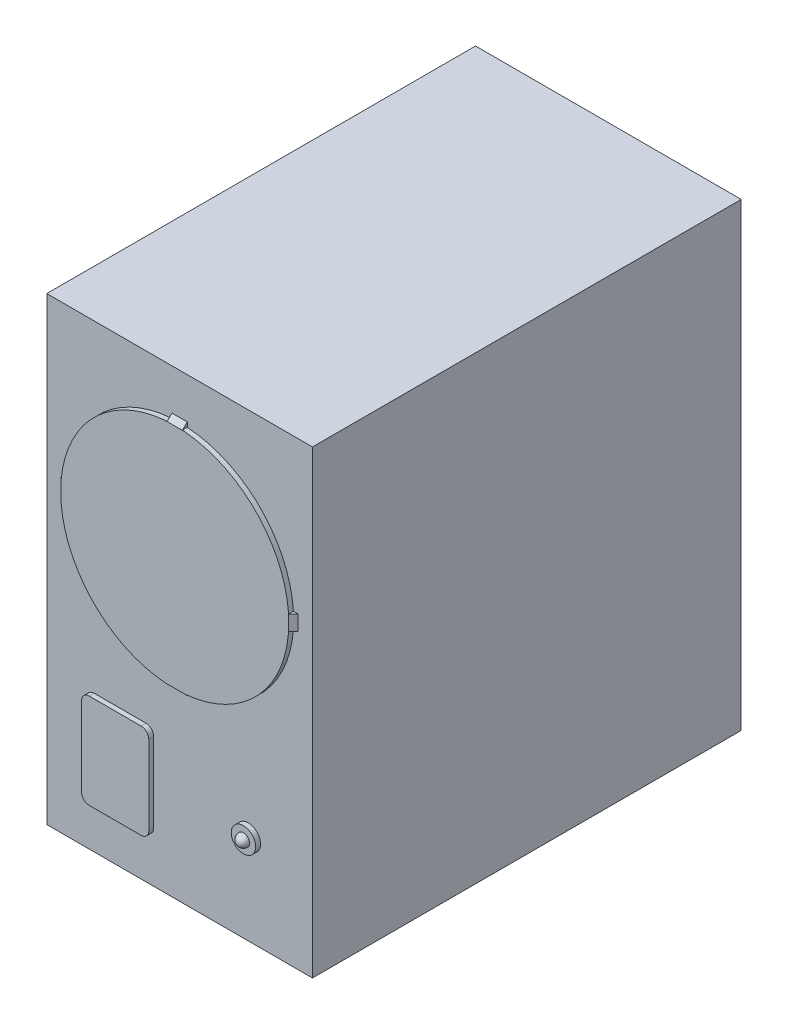
SolidWorks part; units mm, degrees
ref_plane "Plan de face" through (0, 0, 0) normal (0, 0, 1) x (1, 0, 0)
ref_plane "Plan de dessus" through (0, 0, 0) normal (0, 1, 0) x (1, 0, 0)
ref_plane "Plan de droite" through (0, 0, 0) normal (1, 0, 0) x (0, 0, -1)
sketch "Esquisse1" plane through (0, 0, 0) normal (0, 1, 0) x (1, 0, 0)
  line L0 (-43.5, 70.2) -> (43.5, -70.2) construction
  line L1 (-43.5, 70.2) -> (43.5, 70.2)
  line L2 (-43.5, 70.2) -> (-43.5, -70.2)
  line L3 (-43.5, -70.2) -> (43.5, -70.2)
  line L4 (43.5, 70.2) -> (43.5, -70.2)
  point P4 (0, 0)
  dimension "D1" = 87
  dimension "D2" = 140.4
extrude "Boss.-Extru.1" add sketch "Esquisse1" along normal blind 150.6
sketch "Esquisse2" plane through (0, 0, 70.2) normal (0, 0, 1) x (1, 0, 0)
  line L0 (-43.5, 150.6) -> (43.5, 150.6) construction
  line L1 (-43.5, 150.6) -> (43.5, 150.6)
  line L2 (0, 135.75) -> (0, 61.05) construction
  line L3 (-39.7, 100.9) -> (-37.2662, 100.9)
  line L4 (-39.7, 100.9) -> (-39.7, 95.9)
  line L5 (-39.7, 95.9) -> (-37.2662, 95.9)
  line L6 (-37.2662, 100.9) -> (-37.2662, 95.9)
  line L7 (-2.5, 138.1) -> (2.5, 138.1)
  line L8 (-2.5, 138.1) -> (-2.5, 135.6662)
  line L9 (-2.5, 135.6662) -> (2.5, 135.6662)
  line L10 (2.5, 138.1) -> (2.5, 135.6662)
  line L11 (-37.2662, 98.4) -> (37.35, 98.4) construction
  line L12 (37.2662, 100.9) -> (37.2662, 95.9)
  line L13 (39.7, 95.9) -> (37.2662, 95.9)
  line L14 (39.7, 100.9) -> (39.7, 95.9)
  line L15 (39.7, 100.9) -> (37.2662, 100.9)
  line L16 (2.5, 58.7) -> (2.5, 61.1338)
  line L17 (-2.5, 61.1338) -> (2.5, 61.1338)
  line L18 (-2.5, 58.7) -> (-2.5, 61.1338)
  line L19 (-2.5, 58.7) -> (2.5, 58.7)
  line L20 (-43.5, 150.6) -> (-43.5, 0) construction
  line L21 (-30.5, 45) -> (-8.5, 45)
  line L22 (-30.5, 45) -> (-30.5, 14)
  line L23 (-30.5, 14) -> (-8.5, 14)
  line L24 (-8.5, 45) -> (-8.5, 14)
  line L25 (-43.5, 0) -> (43.5, 0) construction
  line L26 (-30.5, 29.5) -> (-8.5, 29.5) construction
  line L27 (-19.5, 45) -> (-19.5, 14) construction
  line L28 (43.5, 150.6) -> (43.5, 0) construction
  arc A0 (-2.5, 135.6662) -> (-37.2662, 100.9) centre (0, 98.4) ccw
  arc A1 (-28, 45) -> (-30.5, 42.5) centre (-28, 42.5) ccw
  arc A2 (-11, 45) -> (-8.5, 42.5) centre (-11, 42.5) cw
  arc A3 (-11, 14) -> (-8.5, 16.5) centre (-11, 16.5) ccw
  arc A4 (-28, 14) -> (-30.5, 16.5) centre (-28, 16.5) cw
  circle A5 centre (22.5, 29.5) radius 4
  arc A6 (37.2662, 100.9) -> (2.5, 135.6662) centre (0, 98.4) ccw
  arc A7 (2.5, 61.1338) -> (37.2662, 95.9) centre (0, 98.4) ccw
  arc A8 (-37.2662, 95.9) -> (-2.5, 61.1338) centre (0, 98.4) ccw
  point P4 (0, 150.6)
  point P5 (0, 135.75)
  point P26 (0, 61.05)
  point P53 (26.5, 29.5)
  dimension "D1" = 74.7
  dimension "D9" = 5
  dimension "D10" = 8
  dimension "D2" = 5
  dimension "D3" = 12.5
  dimension "D4" = 79.4
  dimension "D5" = 31
  dimension "D6" = 22
  dimension "D7" = 13
  dimension "D8" = 14
  dimension "D11" = 17
extrude "Boss.-Extru.5" add sketch "Esquisse2" along normal blind 1.6 contours L6 A8 L17 A7 L12 A6 L9 A0 | L14 L15 L12 L13 | L10 L7 L8 L9 | L6 L3 L4 L5 | L18 L19 L16 L17 | A4 L23 A3 L24 A2 L21 A1 L22 | A5 region at (-38.4831, 98.4, 70.2) region at (0, 98.4, 70.2) region at (0, 136.8831, 70.2) region at (0, 59.9169, 70.2) region at (38.4831, 98.4, 70.2) region at (-19.5, 29.5, 70.2) region at (22.5, 29.5, 70.2)
sketch "Esquisse3" plane through (0, 0, 71.8) normal (0, 0, 1) x (1, 0, 0)
  line L0 (20.5, 29.5) -> (24.5, 29.5) construction
  circle A0 centre (22.5, 29.5) radius 4 construction
  circle A1 centre (22.5, 29.5) radius 4
  circle A2 centre (22.5, 29.5) radius 2
  dimension "4" = 4
revolve "Révolution1" add sketch "Esquisse3" angle 180 about L0 region at (22.5, 30.3488, 71.8)
chamfer "Chanfrein1" distance 2.5 angle 45 4 edges at (0, 58.7, 71.8) (-39.7, 98.4, 71.8) (0, 138.1, 71.8) (39.7, 98.4, 71.8)
sketch "Esquisse4" plane through (0, 0, -70.2) normal (0, 0, -1) x (-1, 0, 0)
  line L0 (-43.5, 0) -> (43.5, 0) construction
  line L1 (-43.5, 0) -> (43.5, 0)
  line L3 (-8, 23) -> (8, 23)
  line L4 (-8, 23) -> (-8, 0)
  line L5 (-8, 0) -> (8, 0)
  line L6 (8, 23) -> (8, 0)
  arc A0 (8, 15) -> (-8, 15) centre (0, 15) ccw
  point P6 (0, 0)
  point P8 (0, 23)
  dimension "D1" = 16
  dimension "D2" = 23
extrude "Boss.-Extru.6" add sketch "Esquisse4" along normal blind 5 contours L6 A0 L4 L1 region at (0, 10.7165, -70.2)
